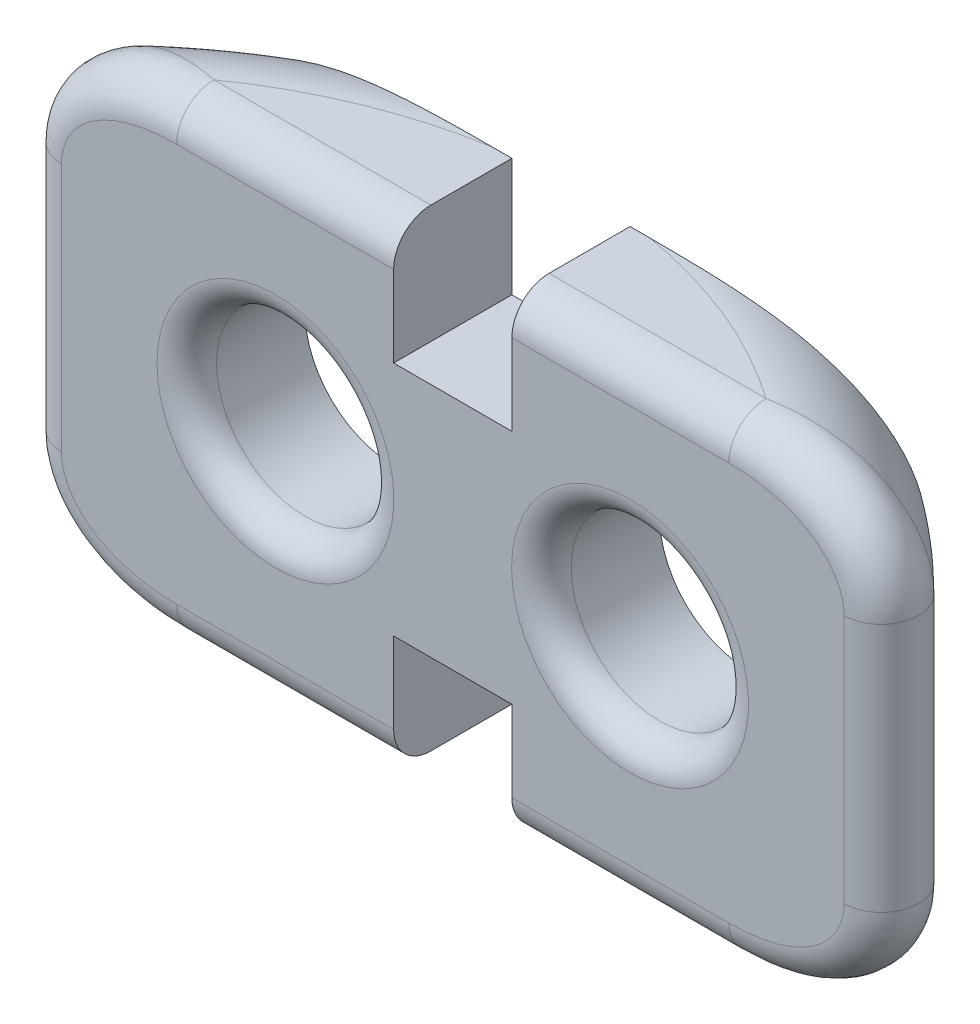
SolidWorks part; units mm, degrees
ref_plane "Front Plane" through (0, 0, 0) normal (0, 0, 1) x (1, 0, 0)
ref_plane "Top Plane" through (0, 0, 0) normal (0, 1, 0) x (1, 0, 0)
ref_plane "Right Plane" through (0, 0, 0) normal (1, 0, 0) x (0, 0, -1)
sketch "Sketch1" plane through (0, 0, 0) normal (0, 0, 1) x (1, 0, 0)
  line L0 (8.89, 6.35) -> (8.89, 0) construction
  line L1 (0, 0) -> (17.78, 0)
  line L2 (0, 0) -> (0, 6.35)
  line L3 (0, 6.35) -> (17.78, 6.35)
  line L4 (17.78, 0) -> (17.78, 6.35)
  line L5 (-0.635, 3.175) -> (8.89, 3.175) construction
  line L6 (8.89, 3.175) -> (18.415, 3.175) construction
  dimension "D1" = 6.35
  dimension "D2" = 17.78
extrude "Boss-Extrude1" add sketch "Sketch1" along normal blind 1.5875
sketch "Sketch2" plane through (0, 0, 1.5875) normal (0, 0, 1) x (1, 0, 0)
  line L0 (6.5087, 3.175) -> (11.2712, 3.175) construction
  line L1 (8.89, 6.35) -> (8.89, 3.175) construction
  line L2 (17.78, 6.35) -> (0, 6.35) construction
  line L3 (8.89, 3.175) -> (8.89, 0) construction
  line L4 (0, 0) -> (17.78, 0) construction
  circle A0 centre (6.5087, 3.175) radius 1.1906
  circle A1 centre (11.2712, 3.175) radius 1.1906
  dimension "D2" = 2.3813
  dimension "D1" = 4.7625
sketch "Sketch4" plane through (0, 0, 1.5875) normal (0, 0, 1) x (1, 0, 0)
  line L0 (8.89, 6.35) -> (8.89, 0) construction
  line L1 (17.78, 6.35) -> (0, 6.35) construction
  line L2 (0, 0) -> (17.78, 0) construction
  line L3 (8.89, 3.175) -> (16.3142, 3.175) construction
  line L4 (9.6837, 0) -> (9.6837, 1.5875)
  line L5 (8.0962, 6.35) -> (9.6837, 6.35)
  line L6 (8.0962, 6.35) -> (8.0962, 4.7625)
  line L7 (8.0962, 4.7625) -> (9.6837, 4.7625)
  line L8 (9.6837, 6.35) -> (9.6837, 4.7625)
  line L9 (8.0962, 1.5875) -> (9.6837, 1.5875)
  line L10 (8.0962, 0) -> (8.0962, 1.5875)
  line L11 (8.0962, 0) -> (9.6837, 0)
  dimension "D1" = 1.5875
  dimension "D2" = 1.5875
extrude "Cut-Extrude1" cut sketch "Sketch4" against normal blind 1.5875
extrude "Cut-Extrude3" cut sketch "Sketch2" against normal through all
fillet "Fillet3" radius 0.4 2 edges at (12.4619, 3.175, 1.5875) (7.6994, 3.175, 1.5875)
sketch "Sketch5" plane through (0, 6.35, 0) normal (0, 1, 0) x (1, 0, 0)
  line L0 (8.89, -1.5875) -> (8.89, -11.1125) construction
  line L1 (8.0962, -1.5875) -> (9.6837, -1.5875) construction
  line L2 (8.0963, -1.5875) -> (0, -1.5875) construction
  line L4 (-3.2576, 6.2458) -> (21.9295, 6.2458)
  line L5 (-3.2576, 6.2458) -> (-3.2576, -20.2609)
  line L6 (-3.2576, -20.2609) -> (21.9295, -20.2609)
  line L7 (21.9295, 6.2458) -> (21.9295, -20.2609)
  circle A0 centre (8.89, -6.35) radius 7.9375
  dimension "D2" = 15.875
  dimension "D1" = 9.525
extrude "Cut-Extrude4" cut sketch "Sketch5" against normal through all
fillet "Fillet5" radius 1.5 4 edges at (14.5027, 0, 0.7373) (14.5027, 6.35, 0.7373) (3.2773, 0, 0.7373) (3.2773, 6.35, 0.7373)
fillet "Fillet4" radius 0.5 10 edges at (11.4525, 0, 1.5875) (14.692, 0.4476, 1.5875) (15.24, 3.175, 1.5875) (11.4525, 6.35, 1.5875) (6.3275, 0, 1.5875) (2.8242, 0.7091, 1.5875) (2.54, 3.175, 1.5875) (3.088, 5.9024, 1.5875) (14.9558, 5.6409, 1.5875) (6.3275, 6.35, 1.5875)
